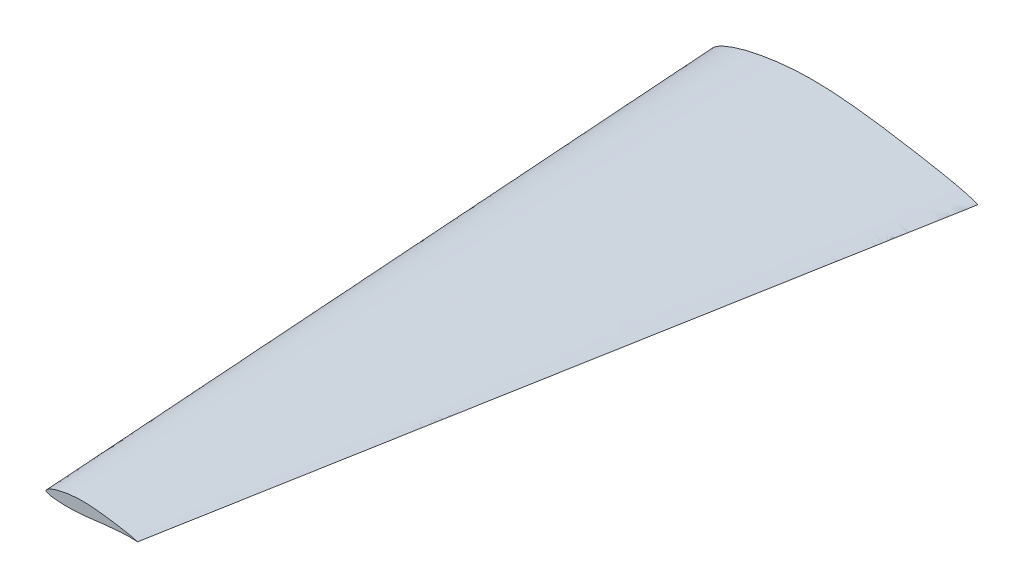
SolidWorks part; units mm, degrees
ref_plane "Front Plane" through (0, 0, 0) normal (0, 0, 1) x (1, 0, 0)
ref_plane "Top Plane" through (0, 0, 0) normal (0, 1, 0) x (1, 0, 0)
ref_plane "Right Plane" through (0, 0, 0) normal (1, 0, 0) x (0, 0, -1)
curve "Curve1"
  spline degree 3 poles (0.9921, 0.0008, 0) (1.0019, -0.0008, 0) (0.9929, 0.0016, 0) (0.9861, 0.0043, 0) (0.9706, 0.0096, 0) (0.9519, 0.0152, 0) (0.9278, 0.021, 0) (0.8992, 0.0273, 0) (0.8662, 0.0341, 0) (0.8293, 0.0413, 0) (0.789, 0.0488, 0) (0.746, 0.0564, 0) (0.7007, 0.0641, 0) (0.6538, 0.0714, 0) (0.6058, 0.0784, 0) (0.5573, 0.0846, 0) (0.5088, 0.0898, 0) (0.4609, 0.0938, 0) (0.4138, 0.0961, 0) (0.3679, 0.0966, 0) (0.3232, 0.0952, 0) (0.2801, 0.092, 0) (0.2388, 0.0874, 0) (0.1997, 0.0815, 0) (0.1631, 0.0746, 0) (0.1296, 0.0669, 0) (0.0993, 0.0585, 0) (0.0726, 0.0496, 0) (0.0499, 0.0404, 0) (0.0312, 0.031, 0) (0.0168, 0.0217, 0) (0.0085, 0.0145, 0) (0.0039, 0.009, 0) (0.0018, 0.0058, 0) (0.0004, 0.0024, 0) (0, 0.0003, 0) (0, -0.0012, 0) (0.0006, -0.0026, 0) (0.002, -0.0043, 0) (0.0049, -0.007, 0) (0.0107, -0.0108, 0) (0.0215, -0.0156, 0) (0.0378, -0.0206, 0) (0.0598, -0.0253, 0) (0.0864, -0.0294, 0) (0.1174, -0.033, 0) (0.1523, -0.036, 0) (0.1908, -0.0383, 0) (0.2323, -0.0397, 0) (0.2764, -0.0402, 0) (0.3228, -0.0395, 0) (0.3711, -0.0373, 0) (0.4212, -0.0335, 0) (0.4729, -0.0284, 0) (0.526, -0.0227, 0) (0.5798, -0.0169, 0) (0.6336, -0.0114, 0) (0.6866, -0.0064, 0) (0.7378, -0.0023, 0) (0.7866, 0.0009, 0) (0.832, 0.0031, 0) (0.8733, 0.0042, 0) (0.9096, 0.0045, 0) (0.9406, 0.0038, 0) (0.9645, 0.0029, 0) (0.984, 0.0013, 0) (0.9921, 0.0008, 0) (1.0019, -0.0008, 0) (0.9929, 0.0016, 0) knots -0.016161 -0.007282 -0.001839 0 0.00178 0.006777 0.014308 0.024046 0.036116 0.050547 0.06713 0.085624 0.105767 0.127282 0.149864 0.17323 0.197069 0.221103 0.245052 0.268663 0.291773 0.314299 0.336178 0.357377 0.377792 0.397225 0.415489 0.432417 0.447849 0.461651 0.473687 0.483898 0.492263 0.498797 0.499955 0.502811 0.504371 0.50536 0.505925 0.506503 0.507535 0.509205 0.512345 0.517665 0.526422 0.537425 0.550643 0.565966 0.583206 0.602155 0.622587 0.644255 0.666998 0.690703 0.715307 0.740824 0.767084 0.793717 0.820331 0.846519 0.871863 0.895937 0.918335 0.938667 0.956573 0.971715 0.983839 0.992718 0.998161 1 1.00178 1.006777 1.014308 periodic
sketch "Sketch1" plane through (0, 0, 0) normal (0, 0, 1) x (1, 0, 0)
  line L0 (1167.2059, -30.8288) -> (-1162.7941, -35.0845) construction
  spline S1 degree 3 poles (1148.7784, -27.977) (1171.7172, -31.8039) (1150.5581, -26.2223) (1134.8254, -19.9356) (1098.6121, -7.5831) (1055.1085, 5.302) (998.7633, 18.7181) (932.1355, 33.1472) (855.1368, 48.7571) (769.1604, 65.315) (675.3297, 82.539) (574.9855, 100.1298) (469.4321, 117.5896) (360.0593, 134.5108) (248.1955, 150.3414) (135.1701, 164.471) (22.251, 176.387) (-89.4773, 185.3614) (-199.1981, 190.448) (-306.2906, 191.3607) (-410.3035, 187.861) (-510.7288, 180.1745) (-606.9241, 169.0794) (-698.0601, 155.2587) (-783.1654, 138.9679) (-861.372, 120.7249) (-931.8769, 100.9237) (-993.9265, 80.0009) (-1046.9152, 58.4337) (-1090.3321, 36.5318) (-1123.8027, 14.8406) (-1143.0848, -2.0984) (-1153.7633, -14.9763) (-1158.687, -22.3942) (-1162.0098, -30.347) (-1162.9632, -35.2319) (-1162.7814, -38.6558) (-1161.4072, -41.8761) (-1158.1965, -46.0146) (-1151.3491, -52.3048) (-1137.7712, -61.0453) (-1112.7076, -72.0855) (-1074.5686, -83.6296) (-1023.3774, -94.5176) (-961.3579, -103.9657) (-889.2059, -112.1487) (-807.7812, -118.8643) (-718.123, -123.9211) (-621.353, -127.1211) (-518.5136, -128.0007) (-410.4966, -125.9274) (-297.9318, -120.4997) (-181.1922, -111.4131) (-60.6773, -99.1751) (62.927, -85.6192) (188.2527, -71.7896) (313.5351, -58.6199) (436.8922, -46.706) (556.3778, -36.7171) (670.0141, -28.9741) (775.8051, -23.5992) (871.9959, -20.7419) (956.4498, -19.9967) (1028.6755, -21.2748) (1084.3745, -23.2358) (1129.9205, -26.8607) (1148.7784, -27.977) (1171.7172, -31.8039) (1150.5581, -26.2223) knots -0.016161 -0.007282 -0.001839 0 0.00178 0.006777 0.014308 0.024046 0.036116 0.050547 0.06713 0.085624 0.105767 0.127282 0.149864 0.17323 0.197069 0.221103 0.245052 0.268663 0.291773 0.314299 0.336178 0.357377 0.377792 0.397225 0.415489 0.432417 0.447849 0.461651 0.473687 0.483898 0.492263 0.498797 0.499955 0.502811 0.504371 0.50536 0.505925 0.506503 0.507535 0.509205 0.512345 0.517665 0.526422 0.537425 0.550643 0.565966 0.583206 0.602155 0.622587 0.644255 0.666998 0.690703 0.715307 0.740824 0.767084 0.793717 0.820331 0.846519 0.871863 0.895937 0.918335 0.938667 0.956573 0.971715 0.983839 0.992718 0.998161 1 1.00178 1.006777 1.014308 only from (1167.2059, -30.8288) to (1167.2059, -30.8288)
  dimension "D1" = 2330
ref_plane "Plane1" through (0, 0, 6200) normal (0, 0, 1) x (1, 0, 0)
ref_plane "Plane3" through (0, -35.0845, 0) normal (0, 1, 0) x (1, 0, 0)
sketch "Sketch4" plane through (0, -35.0845, 0) normal (0, 1, 0) x (1, 0, 0)
  line L1 (1167.2059, 0) -> (-1162.7941, 0) construction
  line L2 (-172.1886, -6200) -> (172.1886, -6200) construction
  line L4 (-1162.7941, 0) -> (-862.7941, -6200)
sketch "Sketch5" plane through (0, 0, 6200) normal (0, 0, 1) x (1, 0, 0)
  line L0 (46.251, -35.2354) -> (-753.7688, -35.3009) construction
  spline S1 degree 3 poles (39.9103, -34.3504) (47.78, -35.5469) (40.5107, -33.741) (35.0952, -31.6671) (22.6402, -27.6181) (7.6874, -23.4229) (-11.663, -19.1093) (-34.5377, -14.4998) (-60.9677, -9.5373) (-90.4749, -4.2947) (-122.6736, 1.1372) (-157.1033, 6.6624) (-193.3153, 12.1171) (-230.8318, 17.3686) (-269.1955, 22.2345) (-307.9483, 26.5125) (-346.6538, 30.0335) (-384.9373, 32.5536) (-422.5145, 33.7529) (-459.1715, 33.5367) (-494.7528, 31.8256) (-529.0855, 28.6992) (-561.9538, 24.4271) (-593.0769, 19.2472) (-622.124, 13.2516) (-648.8002, 6.6219) (-672.8329, -0.5031) (-693.9662, -7.9701) (-711.9952, -15.6131) (-726.7466, -23.3233) (-738.0949, -30.9123) (-744.6106, -36.8049) (-748.2018, -41.2651) (-749.8503, -43.8282) (-750.9483, -46.5664) (-751.2505, -48.243) (-751.1714, -49.4139) (-750.6851, -50.5093) (-749.5659, -51.9099) (-747.1913, -54.0289) (-742.5011, -56.9533) (-733.8685, -60.6082) (-720.7584, -64.3709) (-703.1844, -67.8447) (-681.9116, -70.7722) (-657.1771, -73.2167) (-629.2762, -75.1133) (-598.5656, -76.4015) (-565.4302, -77.0191) (-530.2289, -76.8125) (-493.2702, -75.5698) (-454.7715, -73.1566) (-414.8621, -69.4706) (-373.6761, -64.6873) (-331.4393, -59.4377) (-288.6147, -54.086) (-245.8016, -48.9603) (-203.6413, -44.2739) (-162.7964, -40.2655) (-123.9425, -37.0546) (-87.7619, -34.6929) (-54.8546, -33.2402) (-25.9538, -32.5684) (-1.2281, -32.6493) (17.8446, -33.0456) (33.4506, -34.0614) (39.9103, -34.3504) (47.78, -35.5469) (40.5107, -33.741) knots -0.016161 -0.007282 -0.001839 0 0.00178 0.006777 0.014308 0.024046 0.036116 0.050547 0.06713 0.085624 0.105767 0.127282 0.149864 0.17323 0.197069 0.221103 0.245052 0.268663 0.291773 0.314299 0.336178 0.357377 0.377792 0.397225 0.415489 0.432417 0.447849 0.461651 0.473687 0.483898 0.492263 0.498797 0.499955 0.502811 0.504371 0.50536 0.505925 0.506503 0.507535 0.509205 0.512345 0.517665 0.526422 0.537425 0.550643 0.565966 0.583206 0.602155 0.622587 0.644255 0.666998 0.690703 0.715307 0.740824 0.767084 0.793717 0.820331 0.846519 0.871863 0.895937 0.918335 0.938667 0.956573 0.971715 0.983839 0.992718 0.998161 1 1.00178 1.006777 1.014308 only from (46.2312, -35.2354) to (46.2312, -35.2354)
  dimension "D1" = 800
sketch "Sketch6" plane through (0, 0, 6200) normal (0, 0, 1) x (1, 0, 0)
  line L0 (-753.7688, -35.3009) -> (-751.2083, -48.6103)
  spline S0 degree 3 poles (39.9103, -34.3504) (47.78, -35.5469) (40.5107, -33.741) (35.0952, -31.6671) (22.6402, -27.6181) (7.6874, -23.4229) (-11.663, -19.1093) (-34.5377, -14.4998) (-60.9677, -9.5373) (-90.4749, -4.2947) (-122.6736, 1.1372) (-157.1033, 6.6624) (-193.3153, 12.1171) (-230.8318, 17.3686) (-269.1955, 22.2345) (-307.9483, 26.5125) (-346.6538, 30.0335) (-384.9373, 32.5536) (-422.5145, 33.7529) (-459.1715, 33.5367) (-494.7528, 31.8256) (-529.0855, 28.6992) (-561.9538, 24.4271) (-593.0769, 19.2472) (-622.124, 13.2516) (-648.8002, 6.6219) (-672.8329, -0.5031) (-693.9662, -7.9701) (-711.9952, -15.6131) (-726.7466, -23.3233) (-738.0949, -30.9123) (-744.6106, -36.8049) (-748.2018, -41.2651) (-749.8503, -43.8282) (-750.9483, -46.5664) (-751.2505, -48.243) (-751.1714, -49.4139) (-750.6851, -50.5093) (-749.5659, -51.9099) (-747.1913, -54.0289) (-742.5011, -56.9533) (-733.8685, -60.6082) (-720.7584, -64.3709) (-703.1844, -67.8447) (-681.9116, -70.7722) (-657.1771, -73.2167) (-629.2762, -75.1133) (-598.5656, -76.4015) (-565.4302, -77.0191) (-530.2289, -76.8125) (-493.2702, -75.5698) (-454.7715, -73.1566) (-414.8621, -69.4706) (-373.6761, -64.6873) (-331.4393, -59.4377) (-288.6147, -54.086) (-245.8016, -48.9603) (-203.6413, -44.2739) (-162.7964, -40.2655) (-123.9425, -37.0546) (-87.7619, -34.6929) (-54.8546, -33.2402) (-25.9538, -32.5684) (-1.2281, -32.6493) (17.8446, -33.0456) (33.4506, -34.0614) (39.9103, -34.3504) (47.78, -35.5469) (40.5107, -33.741) knots -0.016161 -0.007282 -0.001839 0 0.00178 0.006777 0.014308 0.024046 0.036116 0.050547 0.06713 0.085624 0.105767 0.127282 0.149864 0.17323 0.197069 0.221103 0.245052 0.268663 0.291773 0.314299 0.336178 0.357377 0.377792 0.397225 0.415489 0.432417 0.447849 0.461651 0.473687 0.483898 0.492263 0.498797 0.499955 0.502811 0.504371 0.50536 0.505925 0.506503 0.507535 0.509205 0.512345 0.517665 0.526422 0.537425 0.550643 0.565966 0.583206 0.602155 0.622587 0.644255 0.666998 0.690703 0.715307 0.740824 0.767084 0.793717 0.820331 0.846519 0.871863 0.895937 0.918335 0.938667 0.956573 0.971715 0.983839 0.992718 0.998161 1 1.00178 1.006777 1.014308 only from (46.2312, -35.2354) to (46.2312, -35.2354) construction
ref_axis "Axis2" through (-751.2083, -48.6103, 6200) along (-0.0662, 0.0022, -0.9978)
loft "Loft5" add profiles "Sketch1", "Sketch5" connector at (-1162.8009, -35.1632, 0) connector at (-751.1274, -47.6465, 6200)
